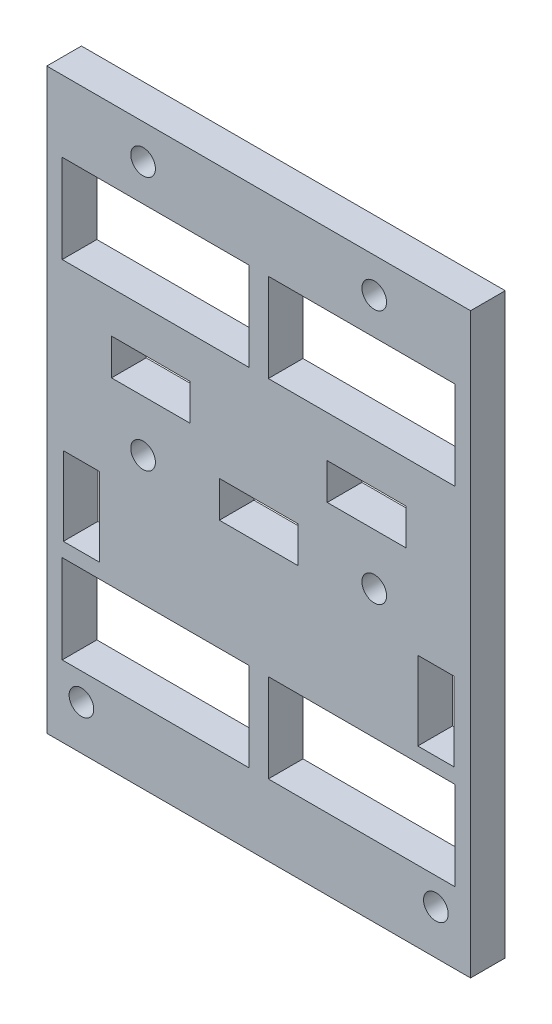
SolidWorks part; units mm, degrees
ref_plane "Front Plane" through (0, 0, 0) normal (0, 0, 1) x (1, 0, 0)
ref_plane "Top Plane" through (0, 0, 0) normal (0, 1, 0) x (1, 0, 0)
ref_plane "Right Plane" through (0, 0, 0) normal (1, 0, 0) x (0, 0, -1)
sketch "Sketch1" plane through (0, 0, 0) normal (0, 0, 1) x (1, 0, 0)
  line L0 (0, -37.5) -> (0, 37.5) construction
  line L1 (-27.5, -37.5) -> (27.5, -37.5)
  line L2 (-27.5, -37.5) -> (-27.5, 37.5)
  line L3 (-27.5, 37.5) -> (27.5, 37.5)
  line L4 (27.5, -37.5) -> (27.5, 37.5)
  line L5 (-27.5, -37.5) -> (27.5, 37.5) construction
  line L6 (-27.5, 37.5) -> (27.5, -37.5) construction
  line L7 (-27.5, 0) -> (27.5, 0) construction
  line L8 (-27.5, 22.5) -> (27.5, 22.5) construction
  line L9 (25.5, 16.75) -> (1.25, 28.25) construction
  line L10 (-25.5, 28.25) -> (-1.25, 28.25)
  line L11 (-25.5, 28.25) -> (-25.5, 16.75)
  line L12 (-25.5, 16.75) -> (-1.25, 16.75)
  line L13 (-1.25, 28.25) -> (-1.25, 16.75)
  line L14 (-25.5, 28.25) -> (-1.25, 16.75) construction
  line L15 (-25.5, 16.75) -> (-1.25, 28.25) construction
  line L16 (25.5, 28.25) -> (1.25, 16.75) construction
  line L17 (1.25, 28.25) -> (1.25, 16.75)
  line L18 (25.5, 16.75) -> (1.25, 16.75)
  line L19 (25.5, 28.25) -> (25.5, 16.75)
  line L20 (25.5, 28.25) -> (1.25, 28.25)
  line L21 (25.5, -28.25) -> (1.25, -16.75) construction
  line L22 (-25.5, -16.75) -> (-1.25, -28.25) construction
  line L23 (-25.5, -28.25) -> (-1.25, -16.75) construction
  line L24 (25.5, -16.75) -> (1.25, -28.25) construction
  line L25 (25.5, -28.25) -> (1.25, -28.25)
  line L26 (25.5, -28.25) -> (25.5, -16.75)
  line L27 (25.5, -16.75) -> (1.25, -16.75)
  line L28 (1.25, -28.25) -> (1.25, -16.75)
  line L29 (-1.25, -28.25) -> (-1.25, -16.75)
  line L30 (-25.5, -16.75) -> (-1.25, -16.75)
  line L31 (-25.5, -28.25) -> (-25.5, -16.75)
  line L32 (-25.5, -28.25) -> (-1.25, -28.25)
  point P0 (0, 0)
  point P12 (-13.375, 22.5)
  point P21 (13.375, 22.5)
  point P30 (13.375, -22.5)
  point P31 (-13.375, -22.5)
  dimension "D1" = 55
  dimension "D2" = 75
  dimension "D3" = 22.5
  dimension "D4" = 24.25
  dimension "D5" = 11.5
  dimension "D6" = 1.25
extrude "Boss-Extrude1" add sketch "Sketch1" along normal blind 4.5
sketch "Sketch2" plane through (0, 0, 4.5) normal (0, 0, 1) x (1, 0, 0)
  line L0 (0, -37.5) -> (0, 37.5) construction
  line L1 (-27.5, -37.5) -> (27.5, -37.5) construction
  line L2 (27.5, 37.5) -> (-27.5, 37.5) construction
  line L3 (-27.5, 0) -> (27.5, 0) construction
  line L4 (-27.5, 37.5) -> (-27.5, -37.5) construction
  line L5 (27.5, -37.5) -> (27.5, 37.5) construction
  line L6 (-15, 0) -> (15, 0) construction
  circle A0 centre (-15, 33) radius 1.6
  circle A1 centre (15, 33) radius 1.6
  circle A2 centre (15, 0) radius 1.6
  circle A3 centre (-15, 0) radius 1.6
  dimension "D1" = 3.2
  dimension "D7" = 3.2
  dimension "D8" = 3.2
  dimension "D2" = 15
  dimension "D3" = 33
  dimension "D4" = 30
  dimension "D5" = 15
  dimension "D6" = 0
extrude "screwHoles" cut sketch "Sketch2" against normal through all
sketch "Sketch3" plane through (0, 0, 4.5) normal (0, 0, 1) x (1, 0, 0)
  line L0 (-27.5, 9) -> (26.0486, 9) construction
  line L1 (-27.5, 37.5) -> (-27.5, -37.5) construction
  line L3 (0, 37.5) -> (0, -37.5) construction
  line L4 (27.5, 37.5) -> (-27.5, 37.5) construction
  line L5 (-27.5, -37.5) -> (27.5, -37.5) construction
  line L6 (19.1, 6.65) -> (8.9, 11.35) construction
  line L7 (-19.1, 11.35) -> (-8.9, 11.35)
  line L8 (-19.1, 11.35) -> (-19.1, 6.65)
  line L9 (-19.1, 6.65) -> (-8.9, 6.65)
  line L10 (-8.9, 11.35) -> (-8.9, 6.65)
  line L11 (-19.1, 11.35) -> (-8.9, 6.65) construction
  line L12 (-19.1, 6.65) -> (-8.9, 11.35) construction
  line L13 (19.1, 11.35) -> (8.9, 6.65) construction
  line L14 (8.9, 11.35) -> (8.9, 6.65)
  line L15 (19.1, 6.65) -> (8.9, 6.65)
  line L16 (19.1, 11.35) -> (19.1, 6.65)
  line L17 (19.1, 11.35) -> (8.9, 11.35)
  line L18 (-27.5, 37.5) -> (-27.5, -37.5) construction
  point P2 (-27.5, 0)
  point P12 (-14, 9)
  point P21 (14, 9)
  dimension "D1" = 10.2
  dimension "D2" = 4.7
  dimension "D3" = 14
  dimension "D4" = 9
extrude "BeltClamp" cut sketch "Sketch3" against normal through all
sketch "Sketch4" plane through (0, 0, 4.5) normal (0, 0, 1) x (1, 0, 0)
  line L0 (-27.5, 0) -> (27.5, 0) construction
  line L1 (-27.5, 37.5) -> (-27.5, -37.5) construction
  line L2 (27.5, -37.5) -> (27.5, 37.5) construction
  line L4 (-5.1, 2.35) -> (5.1, 2.35)
  line L5 (-5.1, 2.35) -> (-5.1, -2.35)
  line L6 (-5.1, -2.35) -> (5.1, -2.35)
  line L7 (5.1, 2.35) -> (5.1, -2.35)
  line L8 (-5.1, 2.35) -> (5.1, -2.35) construction
  line L9 (-5.1, -2.35) -> (5.1, 2.35) construction
  circle A0 centre (-15, 0) radius 1.6 construction
  point P6 (0, 0)
  dimension "D1" = 10.2
  dimension "D2" = 4.7
  dimension "D3" = 0
extrude "Cut-Extrude3" cut sketch "Sketch4" against normal through all
sketch "Sketch5" plane through (0, 0, 4.5) normal (0, 0, 1) x (1, 0, 0)
  line L0 (-27.5, -9.75) -> (27.5, -9.75) construction
  line L1 (-27.5, 37.5) -> (-27.5, -37.5) construction
  line L2 (27.5, -37.5) -> (27.5, 37.5) construction
  line L3 (5.1, -2.35) -> (5.1, 2.35) construction
  line L4 (0, -37.5) -> (0, 37.5) construction
  line L5 (-27.5, -37.5) -> (27.5, -37.5) construction
  line L6 (27.5, 37.5) -> (-27.5, 37.5) construction
  line L7 (-20.65, -14.85) -> (-25.35, -4.65) construction
  line L8 (20.65, -4.65) -> (25.35, -4.65)
  line L9 (20.65, -4.65) -> (20.65, -14.85)
  line L10 (20.65, -14.85) -> (25.35, -14.85)
  line L11 (25.35, -4.65) -> (25.35, -14.85)
  line L12 (20.65, -4.65) -> (25.35, -14.85) construction
  line L13 (20.65, -14.85) -> (25.35, -4.65) construction
  line L14 (-20.65, -4.65) -> (-25.35, -14.85) construction
  line L15 (-25.35, -4.65) -> (-25.35, -14.85)
  line L16 (-20.65, -14.85) -> (-25.35, -14.85)
  line L17 (-20.65, -4.65) -> (-20.65, -14.85)
  line L18 (-20.65, -4.65) -> (-25.35, -4.65)
  line L19 (23, -9.75) -> (23, -37.5) construction
  line L20 (-23, -9.75) -> (-23, -37.5) construction
  circle A0 centre (23, -31.75) radius 1.6
  circle A1 centre (-23, -31.75) radius 1.6
  point P6 (5.1, 0)
  point P15 (23, -9.75)
  point P24 (-23, -9.75)
  dimension "D5" = 3.2
  dimension "D1" = 9.75
  dimension "D2" = 10.2
  dimension "D3" = 4.7
  dimension "D4" = 23
  dimension "D6" = 22
extrude "Cut-Extrude4" cut sketch "Sketch5" against normal through all
sketch "Sketch6" plane through (0, 0, 4.5) normal (0, 0, 1) x (1, 0, 0)
  line L0 (-25.35, -9.75) -> (25.35, -9.75) construction
  line L1 (-25.35, -4.65) -> (-25.35, -14.85) construction
  line L2 (25.35, -14.85) -> (25.35, -4.65) construction
  line L3 (0, -2.35) -> (0, -37.5) construction
  line L4 (-5.1, -2.35) -> (5.1, -2.35) construction
  line L5 (-27.5, -37.5) -> (27.5, -37.5) construction
  line L6 (23, -14.85) -> (23, -4.65) construction
  line L7 (20.65, -14.85) -> (25.35, -14.85) construction
  line L8 (25.35, -4.65) -> (20.65, -4.65) construction
  line L9 (20.65, -4.65) -> (20.65, -14.85) construction
  line L10 (19.65, -15.85) -> (26.35, -15.85)
  line L11 (19.65, -15.85) -> (19.65, -3.65)
  line L12 (19.65, -3.65) -> (26.35, -3.65)
  line L13 (26.35, -15.85) -> (26.35, -3.65)
  line L14 (19.65, -15.85) -> (26.35, -3.65) construction
  line L15 (19.65, -3.65) -> (26.35, -15.85) construction
  line L16 (-19.65, -3.65) -> (-26.35, -15.85) construction
  line L17 (-19.65, -15.85) -> (-26.35, -3.65) construction
  line L18 (-23, -14.85) -> (-23, -4.65) construction
  line L19 (-26.35, -15.85) -> (-26.35, -3.65)
  line L20 (-19.65, -3.65) -> (-26.35, -3.65)
  line L21 (-19.65, -15.85) -> (-19.65, -3.65)
  line L22 (-19.65, -15.85) -> (-26.35, -15.85)
  circle A0 centre (23, -9.75) radius 1.6
  circle A1 centre (-23, -9.75) radius 1.6
  point P18 (23, -9.75)
  dimension "D3" = 3.2
  dimension "D1" = 1
  dimension "D2" = 1
extrude "FrontToRear1" [suppressed] add sketch "Sketch6" against normal up to surface (4.5 mm away) up to face at (-24.6, -31.75, 0)
sketch "Sketch7" plane through (0, 0, 4.5) normal (0, 0, 1) x (1, 0, 0)
  line L0 (5.1, 2.35) -> (-5.1, 2.35) construction
  line L1 (-20, -3.35) -> (20, -3.35)
  line L2 (-20, -3.35) -> (-20, 3.35)
  line L3 (-20, 3.35) -> (20, 3.35)
  line L4 (20, -3.35) -> (20, 3.35)
  line L5 (-20, -3.35) -> (20, 3.35) construction
  line L6 (-20, 3.35) -> (20, -3.35) construction
  circle A0 centre (15, 0) radius 1.6 construction
  point P0 (0, 0)
  dimension "D1" = 1
  dimension "D2" = 5
extrude "FrontToRear2" [suppressed] add sketch "Sketch7" against normal through all
equation "\"X-ROD-SPACING\"=45"
equation "\"Y-ROD-SPACING\"=75"
equation "\"Z-ROD-SPACING\"=17.5"
equation "\"Y-BED-OFFSET\"=2"
equation "\"Y-BED-ROD-INSET\"=3.5"
equation "\"Y-BED-SCREW-SPACING\"=209"
equation "\"Y-BED-SCREW-CUTOUT-SLOT-HEIGHT\"=1"
equation "\"T-SLOT-NUT-FILLET-RADIUS\"=0.25"
equation "\"T-SLOT-SCREW-SHAFT-RADIUS\"=1.75"
equation "\"T-SLOT-SCREW-SHAFT-CUTOUT-LENGTH\"=10.5"
equation "\"T-SLOT-NUT-DEPTH\"=4.2"
equation "\"T-SLOT-NUT-WIDTH\"=3"
equation "\"T-SLOT-NUT-END-DISTANCE\"=8"
equation "\"ACRYLIC-THICKNESS\"=10"
equation "\"ACRYLIC-THICKNESS2\"=4.5"
equation "\"ACRYLIC-TAB-CUTOUT-SIZE\"=\"ACRYLIC-THICKNESS\"+\"ACRYLIC-TAB-TOLERANCE\"*2"
equation "\"ACRYLIC-TAB-WIDTH\"=\"ACRYLIC-THICKNESS\""
equation "\"ACRYLIC-M3-HOLE\"=3.2"
equation "\"SMOOTHROD-CAP-SCREW-DISTANCE\"=20"
equation "\"FRAME-WIDTH-INNER\"=370"
equation "\"NEMA17-HOLE-SPACING\"=31"
equation "\"NEMA17-CENTRAL-CUTOUT\"=22.5"
equation "\"Z-BRACKET-REACH\"=55"
equation "\"Z-ROD-INSET\"=16"
equation "\"TOP-BRACKET-SPACING\"=40"
equation "\"SMOOTHROD-X-LENGTH\"=350"
equation "\"SMOOTHROD-Y-LENGTH\"=350"
equation "\"SMOOTHROD-Z-LENGTH\"=350"
equation "\"SMOOTHROD-TIGHTENING-HEADROOM\"=1"
equation "\"LEADSCREW-Z-LENGTH\"=300"
equation "\"SCREW-LENGTH-FRAME\"=\"ACRYLIC-THICKNESS\" + 10"
equation "\"SCREW-LENGTH-MOTOR\"=\"ACRYLIC-THICKNESS\" + 5"
equation "\"SCREW-HEAD-RADIUS\"=6"
equation "\"PRINTED-X-SMOOTHROD-DIAMETER\"=8.2"
equation "\"PRINTED-X-SMOOTHROD-CUTOUT\"=10"
equation "\"PRINTED-X-BASE-HEIGHT\"=10"
equation "\"PRINTED-LM8UU-CUTOUT-SIZE\"=15.25"
equation "\"PRINTED-LM8UU-CUTOUT-LENGTH\"=24.5"
equation "\"PRINTED-X-IDLER-HEIGHT\"=16"
equation "\"PSU-MOUNTING-WIDTH\"=95"
equation "\"PSU-MOUNTING-HEIGHT\"=177"
equation "\"Y-BELT-TO-ROD-DISTANCE\"=20"
equation "\"SPOOL-HOLDER-ROD-SPACING\"=150"
equation "\"D3@Sketch1\"=\"X-ROD-SPACING\"/2"
equation "\"D4@Sketch1\"=\"ACRYLIC-X-CARRIAGE-LM8UU-CUTOUT-WIDTH\""
equation "\"D1@Boss-Extrude1\"=\"ACRYLIC-THICKNESS2\""
equation "\"D1@Sketch2\"=\"ACRYLIC-M3-HOLE\""
equation "\"D1@Sketch3\"=\"ACRYLIC-TAB-CUTOUT-SIZE\""
equation "\"D2@Sketch3\"=\"ACRYLIC-THICKNESS2\"+\"ACRYLIC-TAB-TOLERANCE\"*2"
equation "\"ACRYLIC-X-CARRIAGE-WIDTH\"=55"
equation "\"ACRYLIC-X-CARRIAGE-HEIGHT\"=75"
equation "\"D1@Sketch1\"=\"ACRYLIC-X-CARRIAGE-WIDTH\""
equation "\"D2@Sketch1\"=\"ACRYLIC-X-CARRIAGE-HEIGHT\""
equation "\"ACRYLIC-X-CARRIAGE-CENTER-TAB-SPACING\"=14"
equation "\"D3@Sketch3\"=\"ACRYLIC-X-CARRIAGE-CENTER-TAB-SPACING\""
equation "\"SCREW-LENGTH-EXTRUDER\"=28"
equation "\"ACRYLIC-X-CARRIAGE-SCREW-SPACING-X\"=15"
equation "\"ACRYLIC-X-CARRIAGE-SCREW-SPACING-Y\"=33"
equation "\"D2@Sketch2\"=\"ACRYLIC-X-CARRIAGE-SCREW-SPACING-X\""
equation "\"D3@Sketch2\"=\"ACRYLIC-X-CARRIAGE-SCREW-SPACING-Y\""
equation "\"D1@Sketch4\"=\"ACRYLIC-TAB-CUTOUT-SIZE\""
equation "\"D2@Sketch4\"=\"ACRYLIC-THICKNESS2\"+\"ACRYLIC-TAB-TOLERANCE\"*2"
equation "\"D2@Sketch5\"=\"ACRYLIC-TAB-CUTOUT-SIZE\""
equation "\"D3@Sketch5\"=\"ACRYLIC-THICKNESS2\"+\"ACRYLIC-TAB-TOLERANCE\"*2"
equation "\"ACRYLIC-X-CARRIAGE-EXTRUDER-SHELF-DEPTH\"=\"ACRYLIC-X-CARRIAGE-EXTRUDER-OFFSET\" + 30"
equation "\"ACRYLIC-X-CARRIAGE-EXTRUDER-BRACE-SPACING\"=23"
equation "\"D4@Sketch5\"=\"ACRYLIC-X-CARRIAGE-EXTRUDER-BRACE-SPACING\""
equation "\"D1@Sketch5\"=\"ACRYLIC-THICKNESS2\"/2 + 7.5"
equation "\"D4@Sketch2\"=\"ACRYLIC-X-CARRIAGE-SCREW-SPACING-X\"*2"
equation "\"D5@Sketch2\"=\"ACRYLIC-X-CARRIAGE-SCREW-SPACING-X\""
equation "\"D7@Sketch2\"=\"ACRYLIC-M3-HOLE\""
equation "\"D8@Sketch2\"=\"ACRYLIC-M3-HOLE\""
equation "\"ACRYLIC-X-CARRIAGE-LM8UU-CUTOUT-WIDTH\"=24.25"
equation "\"ACRYLIC-TAB-TOLERANCE\"=.1"
equation "\"ACRYLIC-X-CARRIAGE-EXTRUDER-OFFSET\"=26"
equation "\"ACRYLIC-X-CARRIAGE-EXTRUDER-ANGLE\"=90"
equation "\"ACRYLIC-X-CARRIAGE-EXTRUDER-BRACE-TAB-OFFSET\"=20"
equation "\"ACRYLIC-X-CARRIAGE-EXTRUDER-BRACE-HEIGHT\"=35"
equation "\"ACRYLIC-X-CARRIAGE-EXTRUDER-BRACE-SCREW-SPACING\"=22"
equation "\"D5@Sketch5\"=\"ACRYLIC-M3-HOLE\""
equation "\"D3@Sketch6\"=\"ACRYLIC-M3-HOLE\""
equation "\"ACRYLIC-X-CARRIAGE-LM8UU-CUTOUT-HEIGHT\"=11.5"
equation "\"ACRYLIC-X-CARRIAGE-DUAL-WIDTH-MULTIPLIER\"=1.65"
equation "\"ACRYLIC-X-CARRIAGE-DUAL-HOTEND-SPACING\"=42"
equation "\"ACRYLIC-X-CARRIAGE-DUAL-WIDTH\"=103"
equation "\"ACRYLIC-X-CARRIAGE-DUAL-HOTEND-SEPARATION\"=35"
equation "\"ACRYLIC-X-CARRIAGE-DUAL-MOUNT-PLATE-DEPTH\"=76"
equation "\"ACRYLIC-X-CARRIAGE-DUAL-MOUNT-BRACE-WIDTH\"=45"
equation "\"ACRYLIC-X-CARRIAGE-DUAL-MOUNT-SCREW-WIDTH\"=40"
equation "\"D5@Sketch1\"=\"ACRYLIC-X-CARRIAGE-LM8UU-CUTOUT-HEIGHT\""
